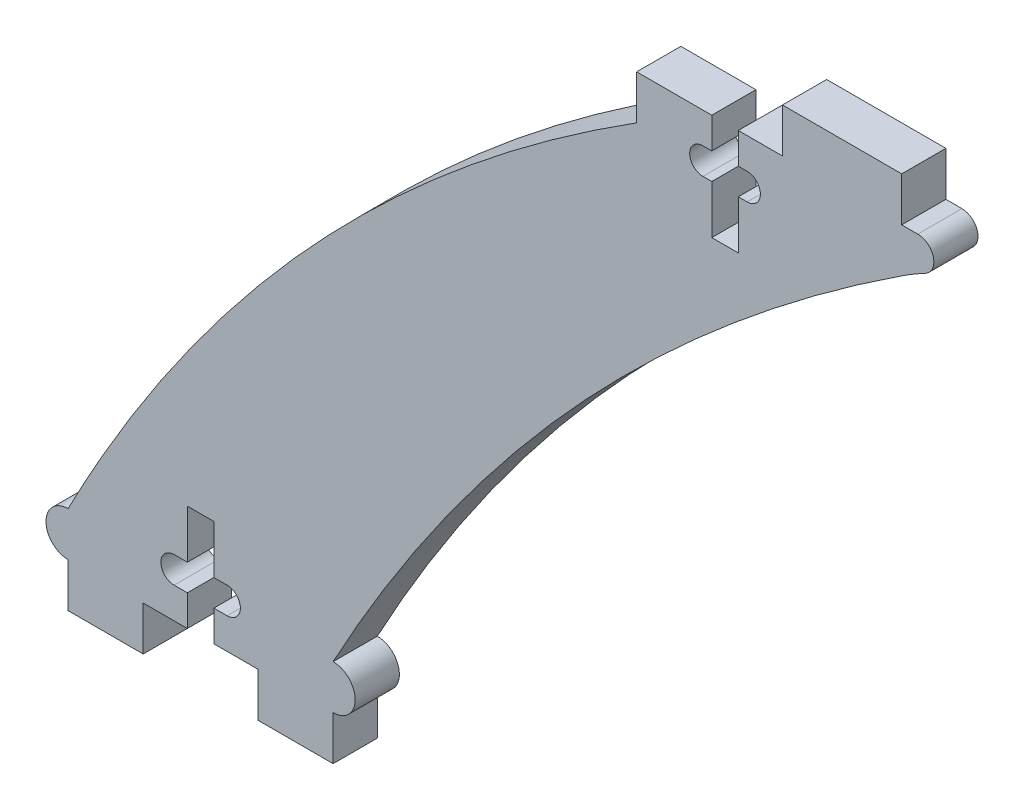
SolidWorks part; units mm, degrees
ref_plane "Front Plane" through (0, 0, 0) normal (0, 0, 1) x (1, 0, 0)
ref_plane "Top Plane" through (0, 0, 0) normal (0, 1, 0) x (1, 0, 0)
ref_plane "Right Plane" through (0, 0, 0) normal (1, 0, 0) x (0, 0, -1)
sketch "Sketch1" plane through (0, 0, 0) normal (0, 0, 1) x (1, 0, 0)
  line L1 (30, 5) -> (0, 5)
  line L2 (30, 5) -> (30, 0)
  line L3 (30, 0) -> (0, 0)
  line L4 (0, 5) -> (0, 0)
  line L5 (94.3604, 75) -> (64.3604, 75)
  line L6 (94.3604, 75) -> (94.3604, 80)
  line L7 (94.3604, 80) -> (64.3604, 80)
  line L8 (64.3604, 75) -> (64.3604, 80)
  spline S0 degree 2 poles (64.3604, 75) (22.6584, 48.7071) (0, 5) knots 0 0 0 1 1 1
  spline S1 degree 2 poles (94.3604, 75) (53.1955, 48.0273) (30, 5) knots 0 0 0 1 1 1
  dimension "D1" = 5
  dimension "D2" = 30
  dimension "D3" = 30
  dimension "D4" = 5
  dimension "D5" = 70
extrude "Boss-Extrude1" add sketch "Sketch1" along normal blind 5 contours L1 L4 L3 L2 | S1 L5 S0 L1 | L8 L5 L6 L7 region at (15, 2.5, 0) region at (41.5599, 40.0466, 0) region at (79.3604, 77.5, 0)
sketch "Sketch3" plane through (0, 0, 5) normal (0, 0, 1) x (1, 0, 0)
  line L0 (94.3604, 80) -> (64.3604, 80) construction
  line L1 (72.8604, 80) -> (75.8604, 80)
  line L2 (72.8604, 80) -> (72.8604, 68)
  line L3 (72.8604, 68) -> (75.8604, 68)
  line L4 (75.8604, 80) -> (75.8604, 68)
  line L5 (71.8604, 75) -> (76.8604, 75) construction
  line L6 (71.8604, 76.5) -> (76.8604, 76.5)
  line L7 (71.8604, 73.5) -> (76.8604, 73.5)
  line L8 (74.3604, 80) -> (74.3604, 68) construction
  line L9 (64.3604, 75) -> (64.3604, 80) construction
  line L10 (13.5, 12) -> (16.5, 12)
  line L11 (13.5, 0) -> (16.5, 0)
  line L12 (15, 12) -> (15, 0) construction
  line L13 (13.5, 12) -> (13.5, 0)
  line L14 (16.5, 12) -> (16.5, 0)
  line L15 (12, 5) -> (18, 5) construction
  line L16 (12, 6.5) -> (18, 6.5)
  line L17 (12, 3.5) -> (18, 3.5)
  line L18 (30, 0) -> (0, 0) construction
  arc A0 (71.8604, 76.5) -> (71.8604, 73.5) centre (71.8604, 75) ccw
  arc A1 (76.8604, 73.5) -> (76.8604, 76.5) centre (76.8604, 75) ccw
  arc A2 (12, 6.5) -> (12, 3.5) centre (12, 5) ccw
  arc A3 (18, 3.5) -> (18, 6.5) centre (18, 5) ccw
  point P8 (74.3604, 75)
  point P23 (15, 5)
  line M1 (30, 0) -> (30, 5)
  spline M2 degree 2 poles (30, 5) (53.1955, 48.0273) (94.3604, 75) knots 0 0 0 1 1 1
  line M3 (94.3604, 75) -> (94.3604, 80)
  line M4 (94.3604, 80) -> (64.3604, 80)
  line M5 (64.3604, 80) -> (64.3604, 75)
  spline M6 degree 2 poles (64.3604, 75) (22.6584, 48.7071) (0, 5) knots 0 0 0 1 1 1
  line M7 (0, 5) -> (0, 0)
  line M8 (0, 0) -> (30, 0)
  dimension "D1" = 3
  dimension "D2" = 12
  dimension "D3" = 3
  dimension "D4" = 8
  dimension "D5" = 5
  dimension "D6" = 10
  dimension "D7" = 3
  dimension "D8" = 12
  dimension "D9" = 5
  dimension "D10" = 3
  dimension "D11" = 6
extrude "Cut-Extrude1" cut sketch "Sketch3" against normal blind 10 flip side to cut contours A3 L17 L14 L4 L6 A1 L7 L3 L2 A0 L13 A2 L16 L10 M8 M1 M2 M3 M4 M5 M6 M7 region at (42.1874, 40.0878, 5)
sketch "Sketch4" plane through (0, 0, 5) normal (0, 0, 1) x (1, 0, 0)
  line L0 (75.8604, 80) -> (75.8604, 76.5) construction
  line L1 (94.3604, 80) -> (80.8604, 80)
  line L2 (94.3604, 80) -> (94.3604, 85)
  line L3 (94.3604, 85) -> (80.8604, 85)
  line L4 (80.8604, 80) -> (80.8604, 85)
  line L5 (13.5, 3.5) -> (13.5, 0) construction
  line L6 (0, 0) -> (8.5, 0)
  line L7 (0, 0) -> (0, -5)
  line L8 (0, -5) -> (8.5, -5)
  line L9 (8.5, 0) -> (8.5, -5)
  line L10 (30, 0) -> (21.5, 0)
  line L11 (30, 0) -> (30, -5)
  line L12 (30, -5) -> (21.5, -5)
  line L13 (21.5, 0) -> (21.5, -5)
  line L14 (-905.6396, 80) -> (49094.3604, 80) construction
  line L15 (94.3604, 75) -> (94.3604, 80) construction
  line L16 (94.2858, 80) -> (96.1774, 80)
  line L17 (-970, 0) -> (49030, 0) construction
  circle A0 centre (110.9435, 50) radius 30
  circle A1 centre (96.1774, 78.183) radius 1.817
  circle A2 centre (30, 2.5) radius 2.5
  circle A3 centre (0, 2.5) radius 2.5
  line M6 (0, 0) -> (13.5, 0)
  line M18 (16.5, 0) -> (30, 0)
  line M19 (30, 0) -> (30, 5)
  line M21 (94.3604, 75) -> (94.3604, 80)
  line M22 (94.3604, 80) -> (75.8604, 80)
  dimension "D5" = 60
  dimension "D1" = 5
  dimension "D2" = 5
  dimension "D3" = 5
  dimension "D4" = 5
extrude "Boss-Extrude2" add sketch "Sketch4" against normal blind 5 contours L4 L1 L2 L3 M22 | A1 | A1 L16 M21 | A1 A0 M21 | L13 L12 L11 M18 | L9 L7 L8 M6 | A2 M19 | A2 M19 | A3 region at (87.6104, 82.5, 5) region at (94.7663, 79.5941, 5) region at (96.1774, 78.183, 5) region at (95.0079, 76.1937, 5) region at (4.25, -2.5, 5) region at (25.75, -2.5, 5) region at (31.061, 2.5, 5) region at (28.939, 2.5, 5)
